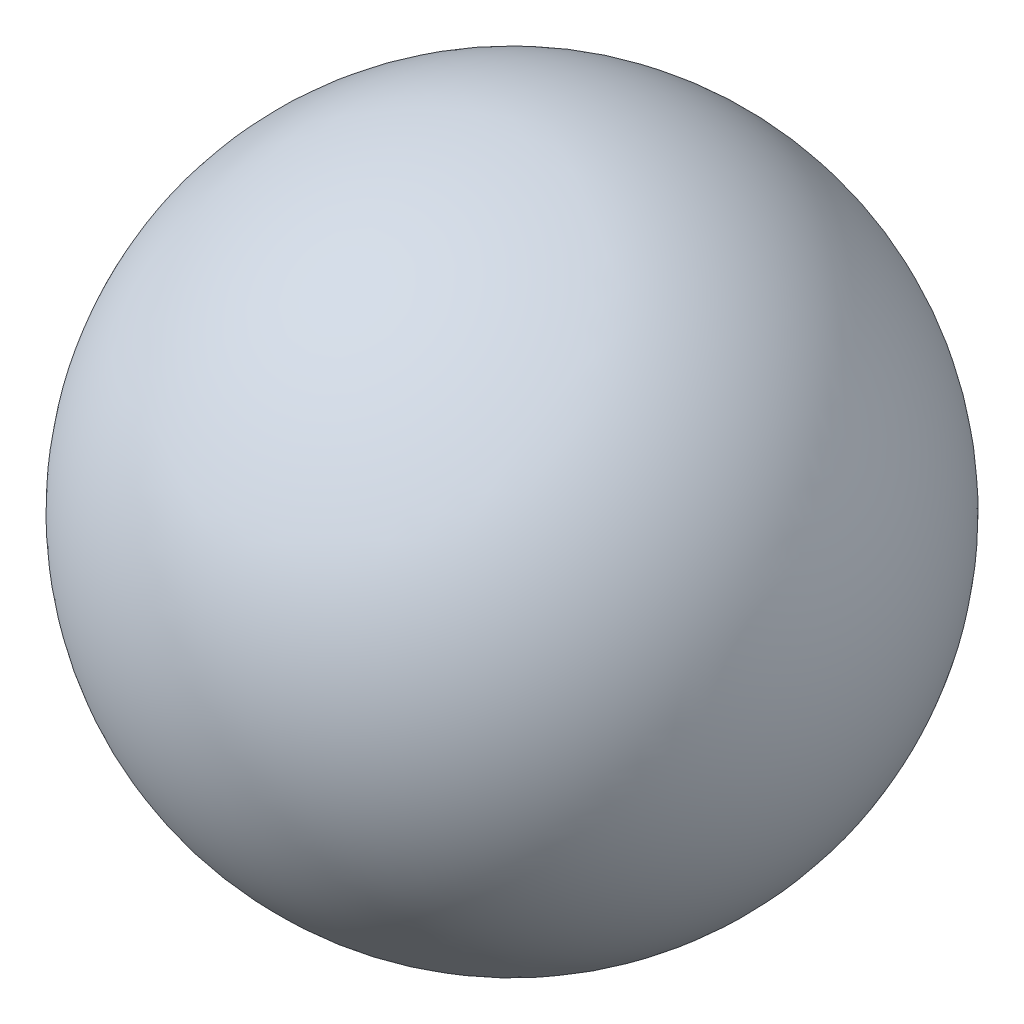
SolidWorks part; units mm, degrees
ref_plane "前基準面" through (0, 0, 0) normal (0, 0, 1) x (1, 0, 0)
ref_plane "上基準面" through (0, 0, 0) normal (0, 1, 0) x (1, 0, 0)
ref_plane "右基準面" through (0, 0, 0) normal (1, 0, 0) x (0, 0, -1)
ref_axis "基準軸1" through (0, -55, 0) along (0, 1, 0)
ref_axis "基準軸2" through (-88.99, 0, 0) along (1, 0, 0)
ref_axis "基準軸3" through (0, 0, 55) along (0, 0, -1)
sketch "草圖1" plane through (0, 0, 0) normal (0, 1, 0) x (1, 0, 0)
  line L0 (-10, 0) -> (10, 0)
  arc A0 (10, 0) -> (-10, 0) centre (0, 0) ccw
  dimension "D1" = 20
revolve "旋轉3" add sketch "草圖1" angle 360 about axis through (-88.99, 0, 0) along (1, 0, 0)
